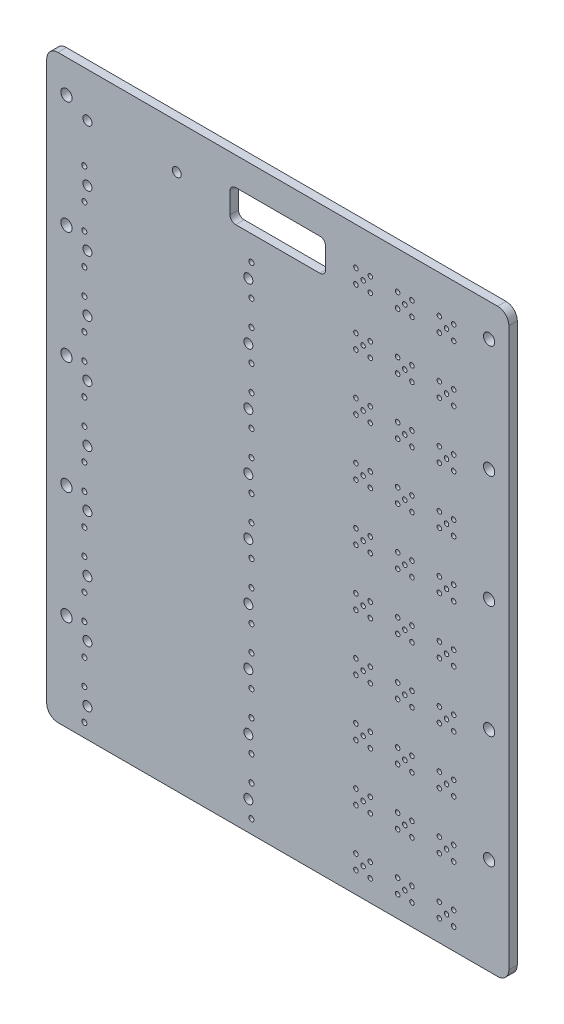
SolidWorks part; units mm, degrees
ref_plane "Front Plane" through (0, 0, 0) normal (0, 0, 1) x (1, 0, 0)
ref_plane "Top Plane" through (0, 0, 0) normal (0, 1, 0) x (1, 0, 0)
ref_plane "Right Plane" through (0, 0, 0) normal (1, 0, 0) x (0, 0, -1)
ref_plane "Plane4" through (0, 0, 0) normal (0, 0, -1) x (-1, 0, 0)
sketch "Sketch1" plane through (0, 0, 0) normal (0, 0, -1) x (-1, 0, 0)
  line L0 (7.475, 96.3) -> (-7.475, 96.3)
  line L1 (-8.475, 97.3) -> (-8.475, 101)
  line L2 (-7.475, 102) -> (7.475, 102)
  line L3 (8.475, 101) -> (8.475, 97.3)
  line L4 (39, 107) -> (-39, 107)
  line L5 (-41, 105) -> (-41, -105)
  line L6 (-39, -107) -> (39, -107)
  line L7 (41, -105) -> (41, 105)
  line L8 (8.475, -101) -> (8.475, -97.3)
  line L9 (-7.475, -102) -> (7.475, -102)
  line L10 (-8.475, -97.3) -> (-8.475, -101)
  line L11 (7.475, -96.3) -> (-7.475, -96.3)
  line L12 (41, -105) -> (41, -107) construction
  line L13 (41, -107) -> (39, -107) construction
  line L14 (41, 0) -> (-41, 0) construction
  line L15 (0, 107) -> (0, -107) construction
  arc A0 (8.475, 97.3) -> (7.475, 96.3) centre (7.475, 97.3) cw
  arc A1 (-7.475, 96.3) -> (-8.475, 97.3) centre (-7.475, 97.3) cw
  arc A2 (-8.475, 101) -> (-7.475, 102) centre (-7.475, 101) cw
  arc A3 (7.475, 102) -> (8.475, 101) centre (7.475, 101) cw
  circle A4 centre (34.325, -40.5) radius 0.45
  circle A5 centre (5.225, -43.25) radius 0.8
  circle A6 centre (-37.5, 21.2) radius 1
  circle A7 centre (5.225, -33.25) radius 0.8
  circle A8 centre (34.325, 46.5) radius 0.45
  circle A9 centre (33.775, -53.25) radius 0.8
  circle A10 centre (34.325, 82) radius 0.45
  circle A11 centre (4.675, 66.5) radius 0.45
  circle A12 centre (33.775, 19.25) radius 0.8
  circle A13 centre (4.675, -0.5) radius 0.45
  circle A14 centre (34.325, 26.5) radius 0.45
  circle A15 centre (5.225, -73.25) radius 0.8
  circle A16 centre (34.325, -66) radius 0.45
  circle A17 centre (5.225, 29.25) radius 0.8
  circle A18 centre (34.325, -80.5) radius 0.45
  circle A19 centre (34.325, 36.5) radius 0.45
  circle A20 centre (4.675, 22) radius 0.45
  circle A21 centre (33.775, -23.25) radius 0.8
  circle A22 centre (5.225, 19.25) radius 0.8
  circle A23 centre (33.775, -13.25) radius 0.8
  circle A24 centre (4.675, -10.5) radius 0.45
  circle A25 centre (34.325, 52) radius 0.45
  circle A26 centre (5.225, 89.25) radius 0.8
  circle A27 centre (5.225, -53.25) radius 0.8
  circle A28 centre (34.325, -70.5) radius 0.45
  circle A29 centre (34.325, -36) radius 0.45
  circle A30 centre (5.225, 59.25) radius 0.8
  circle A31 centre (33.775, 59.25) radius 0.8
  circle A32 centre (34.325, 32) radius 0.45
  circle A33 centre (33.775, -73.25) radius 0.8
  circle A34 centre (4.675, 46.5) radius 0.45
  circle A35 centre (4.675, 26.5) radius 0.45
  circle A36 centre (34.325, -6) radius 0.45
  circle A37 centre (34.325, -20.5) radius 0.45
  circle A38 centre (34.325, -60.5) radius 0.45
  circle A39 centre (5.225, -83.25) radius 0.8
  circle A40 centre (5.225, -13.25) radius 0.8
  circle A41 centre (33.775, -83.25) radius 0.8
  circle A42 centre (34.325, 92) radius 0.45
  circle A43 centre (33.775, -93.25) radius 0.8
  circle A44 centre (4.675, 32) radius 0.45
  circle A45 centre (4.675, 16.5) radius 0.45
  circle A46 centre (34.325, -50.5) radius 0.45
  circle A47 centre (4.675, 76.5) radius 0.45
  circle A48 centre (4.675, 82) radius 0.45
  circle A49 centre (34.325, 16.5) radius 0.45
  circle A50 centre (34.325, -56) radius 0.45
  circle A51 centre (5.225, -3.25) radius 0.8
  circle A52 centre (4.675, 36.5) radius 0.45
  circle A53 centre (4.675, -36) radius 0.45
  circle A54 centre (34.325, 86.5) radius 0.45
  circle A55 centre (33.775, 29.25) radius 0.8
  circle A56 centre (4.675, -26) radius 0.45
  circle A57 centre (4.675, -56) radius 0.45
  circle A58 centre (34.325, -30.5) radius 0.45
  circle A59 centre (33.775, 39.25) radius 0.8
  circle A60 centre (4.675, 56.5) radius 0.45
  circle A61 centre (34.325, 12) radius 0.45
  arc A62 (-39, 107) -> (-41, 105) centre (-39, 105) ccw
  arc A63 (-41, -105) -> (-39, -107) centre (-39, -105) ccw
  arc A64 (39, -107) -> (41, -105) centre (39, -105) ccw
  arc A65 (41, 105) -> (39, 107) centre (39, 105) ccw
  circle A66 centre (5.225, -63.25) radius 0.8
  circle A67 centre (4.675, -6) radius 0.45
  circle A68 centre (5.225, 49.25) radius 0.8
  circle A69 centre (4.675, -16) radius 0.45
  circle A70 centre (33.775, 9.25) radius 0.8
  circle A71 centre (4.675, -76) radius 0.45
  circle A72 centre (34.325, -76) radius 0.45
  circle A73 centre (4.675, -66) radius 0.45
  circle A74 centre (4.675, -30.5) radius 0.45
  circle A75 centre (34.325, 72) radius 0.45
  circle A76 centre (33.775, -63.25) radius 0.8
  circle A77 centre (33.775, 99.25) radius 0.8
  circle A78 centre (4.675, -86) radius 0.45
  circle A79 centre (4.675, 62) radius 0.45
  circle A80 centre (-37.5, 101.2) radius 1
  circle A81 centre (34.325, 76.5) radius 0.45
  circle A82 centre (4.675, -80.5) radius 0.45
  circle A83 centre (33.775, 49.25) radius 0.8
  circle A84 centre (4.675, 86.5) radius 0.45
  circle A85 centre (33.775, -33.25) radius 0.8
  circle A86 centre (4.675, 6.5) radius 0.45
  circle A87 centre (33.775, 79.25) radius 0.8
  circle A88 centre (34.325, -26) radius 0.45
  circle A89 centre (4.675, -60.5) radius 0.45
  circle A90 centre (4.675, 42) radius 0.45
  circle A91 centre (5.225, -23.25) radius 0.8
  circle A92 centre (34.325, 66.5) radius 0.45
  circle A93 centre (5.225, 79.25) radius 0.8
  circle A94 centre (4.675, -20.5) radius 0.45
  circle A95 centre (33.775, 89.25) radius 0.8
  circle A96 centre (17.925, -93.25) radius 0.8
  circle A97 centre (34.325, 22) radius 0.45
  circle A98 centre (4.675, 72) radius 0.45
  circle A99 centre (17.925, 99.25) radius 0.8
  circle A100 centre (4.675, 12) radius 0.45
  circle A101 centre (33.775, -3.25) radius 0.8
  circle A102 centre (34.325, 56.5) radius 0.45
  circle A103 centre (4.675, -70.5) radius 0.45
  circle A104 centre (34.325, -16) radius 0.45
  circle A105 centre (5.225, 39.25) radius 0.8
  circle A106 centre (34.325, -10.5) radius 0.45
  circle A107 centre (4.675, -50.5) radius 0.45
  circle A108 centre (-21.27, -2.0788) radius 0.4
  circle A109 centre (-31.21, -42.0789) radius 0.4
  circle A110 centre (-23.81, -44.6189) radius 0.4
  circle A111 centre (-15.14, -23.3489) radius 0.4
  circle A112 centre (-31.21, -44.6189) radius 0.4
  circle A114 centre (-16.41, -12.0788) radius 0.4
  circle A115 centre (-13.87, -24.6188) radius 0.4
  circle A116 centre (-21.27, -44.6189) radius 0.4
  circle A117 centre (-31.21, -4.6188) radius 0.4
  circle A118 centre (-15.14, -13.3489) radius 0.4
  circle A119 centre (-22.54, -13.3489) radius 0.4
  circle A120 centre (-31.21, -14.6189) radius 0.4
  circle A121 centre (-23.81, -22.0788) radius 0.4
  circle A122 centre (-29.94, -13.3489) radius 0.4
  circle A123 centre (-13.87, -12.0788) radius 0.4
  circle A124 centre (-28.67, -12.0788) radius 0.4
  circle A125 centre (-29.94, -43.3488) radius 0.4
  circle A126 centre (-22.54, -43.3488) radius 0.4
  circle A127 centre (-31.21, -2.0788) radius 0.4
  circle A128 centre (-23.81, -14.6189) radius 0.4
  circle A129 centre (-23.81, -12.0788) radius 0.4
  circle A130 centre (-16.41, -22.0788) radius 0.4
  circle A131 centre (-29.94, -3.3488) radius 0.4
  circle A132 centre (-21.27, -42.0789) radius 0.4
  circle A133 centre (-13.87, -14.6189) radius 0.4
  circle A134 centre (-15.14, -43.3488) radius 0.4
  circle A135 centre (-13.87, -42.0789) radius 0.4
  circle A136 centre (-16.41, -44.6189) radius 0.4
  circle A137 centre (-21.27, -24.6188) radius 0.4
  circle A138 centre (-23.81, -24.6188) radius 0.4
  circle A139 centre (-28.67, -4.6188) radius 0.4
  circle A140 centre (-16.41, -24.6188) radius 0.4
  circle A141 centre (-28.67, -44.6189) radius 0.4
  circle A142 centre (-21.27, -12.0788) radius 0.4
  circle A143 centre (-28.67, -42.0789) radius 0.4
  circle A144 centre (-13.87, -44.6189) radius 0.4
  circle A145 centre (-23.81, -42.0789) radius 0.4
  circle A146 centre (-28.67, -14.6189) radius 0.4
  circle A147 centre (-16.41, -42.0789) radius 0.4
  circle A148 centre (-31.21, -12.0788) radius 0.4
  circle A149 centre (-21.27, -14.6189) radius 0.4
  circle A150 centre (-13.87, -22.0788) radius 0.4
  circle A151 centre (-16.41, -14.6189) radius 0.4
  circle A152 centre (-22.54, -23.3489) radius 0.4
  circle A153 centre (-23.81, -2.0788) radius 0.4
  circle A154 centre (-23.81, -4.6188) radius 0.4
  circle A155 centre (-22.54, -3.3488) radius 0.4
  circle A156 centre (-21.27, -4.6188) radius 0.4
  circle A157 centre (-13.87, -2.0788) radius 0.4
  circle A158 centre (-16.41, -2.0788) radius 0.4
  circle A159 centre (-16.41, -4.6188) radius 0.4
  circle A160 centre (-15.14, -3.3488) radius 0.4
  circle A161 centre (-13.87, -4.6188) radius 0.4
  circle A162 centre (-28.67, -2.0788) radius 0.4
  circle A163 centre (-28.67, 10.4212) radius 0.4
  circle A164 centre (-31.21, 10.4212) radius 0.4
  circle A165 centre (-31.21, 7.8812) radius 0.4
  circle A166 centre (-29.94, 9.1512) radius 0.4
  circle A167 centre (-28.67, 7.8812) radius 0.4
  circle A168 centre (-21.27, 10.4212) radius 0.4
  circle A169 centre (-23.81, 10.4212) radius 0.4
  circle A170 centre (-23.81, 7.8812) radius 0.4
  circle A171 centre (-22.54, 9.1512) radius 0.4
  circle A172 centre (-21.27, 7.8812) radius 0.4
  circle A173 centre (-13.87, -54.6189) radius 0.4
  circle A174 centre (-15.14, -53.3489) radius 0.4
  circle A175 centre (-16.41, -54.6189) radius 0.4
  circle A176 centre (-16.41, -52.0789) radius 0.4
  circle A177 centre (-13.87, -52.0789) radius 0.4
  circle A178 centre (-21.27, -54.6189) radius 0.4
  circle A179 centre (-22.54, -53.3489) radius 0.4
  circle A180 centre (-23.81, -54.6189) radius 0.4
  circle A181 centre (-23.81, -52.0789) radius 0.4
  circle A182 centre (-21.27, -52.0789) radius 0.4
  circle A183 centre (-28.67, -54.6189) radius 0.4
  circle A184 centre (-29.94, -53.3489) radius 0.4
  circle A185 centre (-31.21, -54.6189) radius 0.4
  circle A186 centre (-31.21, -52.0789) radius 0.4
  circle A187 centre (-28.67, -52.0789) radius 0.4
  circle A188 centre (-13.87, 10.4212) radius 0.4
  circle A189 centre (-16.41, 10.4212) radius 0.4
  circle A190 centre (-16.41, 7.8812) radius 0.4
  circle A191 centre (-15.14, 9.1512) radius 0.4
  circle A192 centre (-13.87, 7.8812) radius 0.4
  circle A193 centre (-28.67, 20.4212) radius 0.4
  circle A194 centre (-31.21, 20.4212) radius 0.4
  circle A195 centre (-31.21, 17.8812) radius 0.4
  circle A196 centre (-29.94, 19.1512) radius 0.4
  circle A197 centre (-28.67, 17.8812) radius 0.4
  circle A198 centre (-21.27, 20.4212) radius 0.4
  circle A199 centre (-23.81, 20.4212) radius 0.4
  circle A200 centre (-23.81, 17.8812) radius 0.4
  circle A201 centre (-22.54, 19.1512) radius 0.4
  circle A202 centre (-21.27, 17.8812) radius 0.4
  circle A203 centre (-13.87, 20.4212) radius 0.4
  circle A204 centre (-16.41, 20.4212) radius 0.4
  circle A205 centre (-16.41, 17.8812) radius 0.4
  circle A206 centre (-15.14, 19.1512) radius 0.4
  circle A207 centre (-13.87, 17.8812) radius 0.4
  circle A208 centre (-28.67, 30.4212) radius 0.4
  circle A209 centre (-31.21, 30.4212) radius 0.4
  circle A210 centre (-31.21, 27.8812) radius 0.4
  circle A211 centre (-29.94, 29.1512) radius 0.4
  circle A212 centre (-28.67, 27.8812) radius 0.4
  circle A213 centre (-21.27, 30.4212) radius 0.4
  circle A214 centre (-23.81, 30.4212) radius 0.4
  circle A215 centre (-23.81, 27.8812) radius 0.4
  circle A216 centre (-22.54, 29.1512) radius 0.4
  circle A217 centre (-21.27, 27.8812) radius 0.4
  circle A218 centre (-13.87, 30.4212) radius 0.4
  circle A219 centre (-16.41, 30.4212) radius 0.4
  circle A220 centre (-16.41, 27.8812) radius 0.4
  circle A221 centre (-15.14, 29.1512) radius 0.4
  circle A222 centre (-13.87, 27.8812) radius 0.4
  circle A223 centre (-28.67, 40.4211) radius 0.4
  circle A224 centre (-31.21, 40.4211) radius 0.4
  circle A225 centre (-31.21, 37.8812) radius 0.4
  circle A226 centre (-29.94, 39.1512) radius 0.4
  circle A227 centre (-28.67, 37.8812) radius 0.4
  circle A228 centre (-13.87, -64.6188) radius 0.4
  circle A229 centre (-15.14, -63.3488) radius 0.4
  circle A230 centre (-16.41, -64.6188) radius 0.4
  circle A231 centre (-16.41, -62.0789) radius 0.4
  circle A232 centre (-13.87, -62.0789) radius 0.4
  circle A233 centre (-21.27, -64.6188) radius 0.4
  circle A234 centre (-22.54, -63.3488) radius 0.4
  circle A235 centre (-23.81, -64.6188) radius 0.4
  circle A236 centre (-23.81, -62.0789) radius 0.4
  circle A237 centre (-21.27, -62.0789) radius 0.4
  circle A238 centre (-28.67, -64.6188) radius 0.4
  circle A239 centre (-29.94, -63.3488) radius 0.4
  circle A240 centre (-31.21, -64.6188) radius 0.4
  circle A241 centre (-31.21, -62.0789) radius 0.4
  circle A242 centre (-28.67, -62.0789) radius 0.4
  circle A243 centre (-21.27, 40.4211) radius 0.4
  circle A244 centre (-23.81, 40.4211) radius 0.4
  circle A245 centre (-23.81, 37.8812) radius 0.4
  circle A246 centre (-22.54, 39.1512) radius 0.4
  circle A247 centre (-21.27, 37.8812) radius 0.4
  circle A248 centre (-13.87, 40.4211) radius 0.4
  circle A249 centre (-16.41, 40.4211) radius 0.4
  circle A250 centre (-16.41, 37.8812) radius 0.4
  circle A251 centre (-15.14, 39.1512) radius 0.4
  circle A252 centre (-13.87, 37.8812) radius 0.4
  circle A253 centre (-28.67, 50.4211) radius 0.4
  circle A254 centre (-31.21, 50.4211) radius 0.4
  circle A255 centre (-31.21, 47.8811) radius 0.4
  circle A256 centre (-29.94, 49.1512) radius 0.4
  circle A257 centre (-28.67, 47.8811) radius 0.4
  circle A258 centre (-21.27, 50.4211) radius 0.4
  circle A259 centre (-23.81, 50.4211) radius 0.4
  circle A260 centre (-23.81, 47.8811) radius 0.4
  circle A261 centre (-22.54, 49.1512) radius 0.4
  circle A262 centre (-21.27, 47.8811) radius 0.4
  circle A263 centre (-13.87, 50.4211) radius 0.4
  circle A264 centre (-16.41, 50.4211) radius 0.4
  circle A265 centre (-16.41, 47.8811) radius 0.4
  circle A266 centre (-15.14, 49.1512) radius 0.4
  circle A267 centre (-13.87, 47.8811) radius 0.4
  circle A268 centre (-28.67, 60.4211) radius 0.4
  circle A269 centre (-31.21, 60.4211) radius 0.4
  circle A270 centre (-31.21, 57.8811) radius 0.4
  circle A271 centre (-29.94, 59.1512) radius 0.4
  circle A272 centre (-28.67, 57.8811) radius 0.4
  circle A273 centre (-21.27, 60.4211) radius 0.4
  circle A274 centre (-23.81, 60.4211) radius 0.4
  circle A275 centre (-23.81, 57.8811) radius 0.4
  circle A276 centre (-22.54, 59.1512) radius 0.4
  circle A277 centre (-21.27, 57.8811) radius 0.4
  circle A278 centre (-13.87, 60.4211) radius 0.4
  circle A279 centre (-16.41, 60.4211) radius 0.4
  circle A280 centre (-16.41, 57.8811) radius 0.4
  circle A281 centre (-15.14, 59.1512) radius 0.4
  circle A282 centre (-13.87, 57.8811) radius 0.4
  circle A283 centre (-13.87, -74.6188) radius 0.4
  circle A284 centre (-15.14, -73.3489) radius 0.4
  circle A285 centre (-16.41, -74.6188) radius 0.4
  circle A286 centre (-16.41, -72.0789) radius 0.4
  circle A287 centre (-13.87, -72.0789) radius 0.4
  circle A288 centre (-21.27, -74.6188) radius 0.4
  circle A289 centre (-22.54, -73.3489) radius 0.4
  circle A290 centre (-23.81, -74.6188) radius 0.4
  circle A291 centre (-23.81, -72.0789) radius 0.4
  circle A292 centre (-21.27, -72.0789) radius 0.4
  circle A293 centre (-28.67, -74.6188) radius 0.4
  circle A294 centre (-29.94, -73.3489) radius 0.4
  circle A295 centre (-31.21, -74.6188) radius 0.4
  circle A296 centre (-31.21, -72.0789) radius 0.4
  circle A297 centre (-28.67, -72.0789) radius 0.4
  circle A298 centre (-28.67, 70.4211) radius 0.4
  circle A299 centre (-31.21, 70.4211) radius 0.4
  circle A300 centre (-31.21, 67.8812) radius 0.4
  circle A301 centre (-29.94, 69.1512) radius 0.4
  circle A302 centre (-28.67, 67.8812) radius 0.4
  circle A303 centre (-21.27, 70.4211) radius 0.4
  circle A304 centre (-23.81, 70.4211) radius 0.4
  circle A305 centre (-23.81, 67.8812) radius 0.4
  circle A306 centre (-22.54, 69.1512) radius 0.4
  circle A307 centre (-21.27, 67.8812) radius 0.4
  circle A308 centre (-13.87, 70.4211) radius 0.4
  circle A309 centre (-16.41, 70.4211) radius 0.4
  circle A310 centre (-16.41, 67.8812) radius 0.4
  circle A311 centre (-15.14, 69.1512) radius 0.4
  circle A312 centre (-13.87, 67.8812) radius 0.4
  circle A313 centre (-28.67, 80.4211) radius 0.4
  circle A314 centre (-31.21, 80.4211) radius 0.4
  circle A315 centre (-31.21, 77.8812) radius 0.4
  circle A316 centre (-29.94, 79.1512) radius 0.4
  circle A317 centre (-28.67, 77.8812) radius 0.4
  circle A318 centre (-21.27, 80.4211) radius 0.4
  circle A319 centre (-23.81, 80.4211) radius 0.4
  circle A320 centre (-23.81, 77.8812) radius 0.4
  circle A321 centre (-22.54, 79.1512) radius 0.4
  circle A322 centre (-21.27, 77.8812) radius 0.4
  circle A323 centre (-13.87, 80.4211) radius 0.4
  circle A324 centre (-16.41, 80.4211) radius 0.4
  circle A325 centre (-16.41, 77.8812) radius 0.4
  circle A326 centre (-15.14, 79.1512) radius 0.4
  circle A327 centre (-13.87, 77.8812) radius 0.4
  circle A328 centre (-28.67, 90.4212) radius 0.4
  circle A329 centre (-31.21, 90.4212) radius 0.4
  circle A330 centre (-31.21, 87.8812) radius 0.4
  circle A331 centre (-29.94, 89.1512) radius 0.4
  circle A332 centre (-28.67, 87.8812) radius 0.4
  circle A333 centre (-21.27, 90.4212) radius 0.4
  circle A334 centre (-23.81, 90.4212) radius 0.4
  circle A335 centre (-23.81, 87.8812) radius 0.4
  circle A336 centre (-22.54, 89.1512) radius 0.4
  circle A337 centre (-21.27, 87.8812) radius 0.4
  circle A338 centre (-13.87, -84.6188) radius 0.4
  circle A339 centre (-15.14, -83.3488) radius 0.4
  circle A340 centre (-16.41, -84.6188) radius 0.4
  circle A341 centre (-16.41, -82.0789) radius 0.4
  circle A342 centre (-13.87, -82.0789) radius 0.4
  circle A343 centre (-21.27, -84.6188) radius 0.4
  circle A344 centre (-22.54, -83.3488) radius 0.4
  circle A345 centre (-23.81, -84.6188) radius 0.4
  circle A346 centre (-23.81, -82.0789) radius 0.4
  circle A347 centre (-21.27, -82.0789) radius 0.4
  circle A348 centre (-28.67, -84.6188) radius 0.4
  circle A349 centre (-29.94, -83.3488) radius 0.4
  circle A350 centre (-31.21, -84.6188) radius 0.4
  circle A351 centre (-31.21, -82.0789) radius 0.4
  circle A352 centre (-28.67, -82.0789) radius 0.4
  circle A353 centre (-13.87, 90.4212) radius 0.4
  circle A354 centre (-16.41, 90.4212) radius 0.4
  circle A355 centre (-16.41, 87.8812) radius 0.4
  circle A356 centre (-15.14, 89.1512) radius 0.4
  circle A357 centre (-13.87, 87.8812) radius 0.4
  circle A358 centre (4.675, -40.5) radius 0.45
  circle A359 centre (34.325, -46) radius 0.45
  circle A360 centre (34.325, 6.5) radius 0.45
  circle A361 centre (4.675, 92) radius 0.45
  circle A362 centre (34.325, 62) radius 0.45
  circle A363 centre (34.325, -86) radius 0.45
  circle A364 centre (4.675, -46) radius 0.45
  circle A365 centre (34.325, 42) radius 0.45
  circle A366 centre (5.225, 69.25) radius 0.8
  circle A367 centre (33.775, 69.25) radius 0.8
  circle A368 centre (33.775, -43.25) radius 0.8
  circle A369 centre (5.225, 9.25) radius 0.8
  circle A370 centre (4.675, 52) radius 0.45
  circle A371 centre (34.325, -0.5) radius 0.45
  circle A372 centre (-13.87, -92.0789) radius 0.4
  circle A373 centre (-31.21, -94.6188) radius 0.4
  circle A374 centre (-28.67, -92.0789) radius 0.4
  circle A375 centre (-28.67, -94.6188) radius 0.4
  circle A376 centre (-29.94, -93.3488) radius 0.4
  circle A377 centre (-23.81, -92.0789) radius 0.4
  circle A378 centre (-16.41, -94.6188) radius 0.4
  circle A379 centre (-21.27, -94.6188) radius 0.4
  circle A380 centre (-21.27, -92.0789) radius 0.4
  circle A381 centre (-23.81, -94.6188) radius 0.4
  circle A382 centre (-16.41, -92.0789) radius 0.4
  circle A383 centre (-31.21, -92.0789) radius 0.4
  circle A384 centre (-22.54, -93.3488) radius 0.4
  circle A385 centre (-13.87, -94.6188) radius 0.4
  circle A386 centre (-15.14, -93.3488) radius 0.4
  circle A387 centre (-21.27, -22.0788) radius 0.4
  circle A388 centre (-28.67, -24.6188) radius 0.4
  circle A389 centre (-29.94, -23.3489) radius 0.4
  circle A390 centre (-31.21, -24.6188) radius 0.4
  circle A391 centre (-31.21, -22.0788) radius 0.4
  circle A392 centre (-28.67, -22.0788) radius 0.4
  circle A393 centre (-13.87, -34.6189) radius 0.4
  circle A394 centre (-15.14, -33.3488) radius 0.4
  circle A395 centre (-16.41, -34.6189) radius 0.4
  circle A396 centre (-16.41, -32.0789) radius 0.4
  circle A397 centre (-13.87, -32.0789) radius 0.4
  circle A398 centre (-21.27, -34.6189) radius 0.4
  circle A399 centre (-22.54, -33.3488) radius 0.4
  circle A400 centre (-23.81, -34.6189) radius 0.4
  circle A401 centre (-23.81, -32.0789) radius 0.4
  circle A402 centre (-21.27, -32.0789) radius 0.4
  circle A403 centre (-28.67, -34.6189) radius 0.4
  circle A404 centre (-29.94, -33.3488) radius 0.4
  circle A405 centre (-31.21, -34.6189) radius 0.4
  circle A406 centre (-31.21, -32.0789) radius 0.4
  circle A407 centre (-28.67, -32.0789) radius 0.4
  circle A408 centre (-37.5, -81.2) radius 1
  circle A409 centre (37.5, 81.2) radius 1
  circle A412 centre (-37.5, 41.2) radius 1
  circle A413 centre (-37.5, -41.2) radius 1
  circle A414 centre (-37.5, -101.2) radius 1
  circle A415 centre (-37.5, 61.2) radius 1
  circle A416 centre (37.5, 61.2) radius 1
  circle A417 centre (-37.5, 81.2) radius 1
  circle A420 centre (-37.5, -61.2) radius 1
  circle A421 centre (37.5, 41.2) radius 1
  circle A422 centre (-37.5, -21.2) radius 1
  circle A423 centre (37.5, 101.2) radius 1
  circle A424 centre (37.5, 21.2) radius 1
  arc A425 (8.475, -97.3) -> (7.475, -96.3) centre (7.475, -97.3) ccw
  arc A426 (7.475, -102) -> (8.475, -101) centre (7.475, -101) ccw
  arc A427 (-8.475, -101) -> (-7.475, -102) centre (-7.475, -101) ccw
  arc A428 (-7.475, -96.3) -> (-8.475, -97.3) centre (-7.475, -97.3) ccw
  point P876 (0, 102)
  dimension "D3" = 2
  dimension "D4" = 1
  dimension "D9" = 2
  dimension "D1" = 82
  dimension "D2" = 214
  dimension "D5" = 16.95
  dimension "D6" = 5.7
  dimension "D7" = 5
  dimension "D8" = 5
  dimension "D10" = 5.8
  dimension "D11" = 3.5
  dimension "D12" = 20
extrude "Boss-Extrude1" [suppressed] add sketch "Sketch1" against normal blind 1.5
sketch "Sketch2" plane through (0, 0, 0) normal (0, 0, 1) x (1, 0, 0)
  line L0 (82, 103) -> (0, 103)
  line L1 (0, 103) -> (0, 0)
  line L2 (0, 0) -> (82, 0)
  line L3 (82, 0) -> (82, 103)
  dimension "D1" = 82
  dimension "D2" = 103
extrude "mainBoard" add sketch "Sketch2" along normal blind 1.5
ref_plane "X_mirror" through (41, 0, 0) normal (-1, 0, 0) x (0, 0, 1)
sketch "Sketch3" plane through (0, 0, 1.5) normal (0, 0, 1) x (1, 0, 0)
  line L0 (82, 103) -> (0, 103) construction
  line L1 (41, 103) -> (41, 0) construction
  line L2 (0, 0) -> (82, 0) construction
  line L5 (32.525, 98) -> (49.475, 98)
  line L6 (32.525, 98) -> (32.525, 92.3)
  line L7 (32.525, 92.3) -> (49.475, 92.3)
  line L8 (49.475, 98) -> (49.475, 92.3)
  point P6 (41, 98)
  dimension "D1" = 5
  dimension "D3" = 16.95
  dimension "D4" = 5.7
extrude "solarHole" cut sketch "Sketch3" against normal through all
fillet "Fillet1" radius 2 4 edges at (0, 0, 0.75) (82, 0, 0.75) (82, 103, 0.75) (0, 103, 0.75)
fillet "Fillet2" radius 1 4 edges at (49.475, 92.3, 0.75) (49.475, 98, 0.75) (32.525, 92.3, 0.75) (32.525, 98, 0.75)
hole_wizard "Ø2.0mm Hole_screw" positions "Sketch4" profile "Sketch5" hole size "Ø2.0" standard "ANSI Metric"
sketch "Sketch4" plane through (0, 0, 1.5) normal (0, 0, 1) x (1, 0, 0)
  line L0 (80, 103) -> (2, 103) construction
  line L1 (0, 101) -> (0, 2) construction
  point P0 (3.5, 97.2)
  dimension "D1" = 5.8
  dimension "D2" = 3.5
sketch "Sketch5" plane through (3.5, 97.2, 1.5) normal (1, 0, 0) x (0, -1, 0)
  line L0 (0, 0) -> (0, 10.1259)
  line L1 (0, 10.1259) -> (1, 9.525)
  line L2 (1, 9.525) -> (1, 0)
  line L5 (1, 0) -> (0, 0)
  line L10 (0, 10.1259) -> (-1, 9.525) construction
  line L11 (0, -6.35) -> (0, 107.95) construction
  dimension "Hole Dia." = 2
  dimension "Hole Depth" = 9.525
  dimension "Drill Angle" = 118
hole_wizard "Ø1.6mm Hole_20pin" positions "Sketch12" profile "Sketch13" hole size "Ø1.5" standard "ANSI Metric"
sketch "Sketch12" plane through (0, 0, 1.5) normal (0, 0, 1) x (1, 0, 0)
  line L0 (80, 103) -> (2, 103) construction
  line L1 (0, 101) -> (0, 2) construction
  point P0 (7.225, 95.15)
  point P2 (23.075, 95.15)
  dimension "D1" = 15.85
  dimension "D2" = 7.85
  dimension "D3" = 7.225
sketch "Sketch13" plane through (7.225, 95.15, 1.5) normal (1, 0, 0) x (0, -1, 0)
  line L0 (0, 0) -> (0, 10.0057)
  line L1 (0, 10.0057) -> (0.8, 9.525)
  line L2 (0.8, 9.525) -> (0.8, 0)
  line L5 (0.8, 0) -> (0, 0)
  line L10 (0, 10.0057) -> (-0.8, 9.525) construction
  line L11 (0, -6.35) -> (0, 107.95) construction
  dimension "Hole Dia." = 1.6
  dimension "Hole Depth" = 9.525
  dimension "Drill Angle" = 118
hole_wizard "Ø1.6mm Hole_40pn_big" positions "Sketch6" profile "Sketch7" hole size "Ø1.5" standard "ANSI Metric"
sketch "Sketch6" plane through (0, 0, 1.5) normal (0, 0, 1) x (1, 0, 0)
  line L0 (0, 101) -> (0, 2) construction
  line L1 (80, 103) -> (2, 103) construction
  point P14 (7.225, 85.15)
  point P16 (35.775, 85.15)
  dimension "D1" = 7.225
  dimension "D7" = 17.85
  dimension "D8" = 28.55
sketch "Sketch7" plane through (7.225, 85.15, 1.5) normal (1, 0, 0) x (0, -1, 0)
  line L0 (0, 0) -> (0, 10.0057)
  line L1 (0, 10.0057) -> (0.8, 9.525)
  line L2 (0.8, 9.525) -> (0.8, 0)
  line L5 (0.8, 0) -> (0, 0)
  line L10 (0, 10.0057) -> (-0.8, 9.525) construction
  line L11 (0, -6.35) -> (0, 107.95) construction
  dimension "Hole Dia." = 1.6
  dimension "Hole Depth" = 9.525
  dimension "Drill Angle" = 118
hole_wizard "Ø0.9mm Hole_40pin_tiny" positions "Sketch10" profile "Sketch11" hole size "Ø1.5" standard "ANSI Metric"
sketch "Sketch10" plane through (0, 0, 1.5) normal (0, 0, 1) x (1, 0, 0)
  line L1 (7.225, 85.15) -> (35.775, 85.15) construction
  line L3 (21.5, -11.0236) -> (21.5, 181.3236) construction
  circle A0 centre (7.225, 85.15) radius 0.8 construction
  point P0 (6.675, 87.9)
  point P24 (21.5, 85.15)
  point P25 (21.5, 85.15)
  point P27 (6.675, 82.4)
  point P29 (36.325, 87.9)
  point P30 (36.325, 82.4)
  dimension "D1" = 0.55
  dimension "D2" = 5.5
sketch "Sketch11" plane through (6.675, 87.9, 1.5) normal (1, 0, 0) x (0, -1, 0)
  line L0 (0, 0) -> (0, 9.7954)
  line L1 (0, 9.7954) -> (0.45, 9.525)
  line L2 (0.45, 9.525) -> (0.45, 0)
  line L5 (0.45, 0) -> (0, 0)
  line L10 (0, 9.7954) -> (-0.45, 9.525) construction
  line L11 (0, -6.35) -> (0, 107.95) construction
  dimension "Hole Dia." = 0.9
  dimension "Hole Depth" = 9.525
  dimension "Drill Angle" = 118
hole_wizard "Ø0.8mm MMCX Hole" positions "Sketch8" profile "Sketch9" hole size "Ø1.0" standard "ANSI Metric"
sketch "Sketch8" plane through (0, 0, 1.5) normal (0, 0, 1) x (1, 0, 0)
  line L0 (69.67, 86.32) -> (72.21, 83.78) construction
  line L2 (80, 103) -> (2, 103) construction
  line L3 (82, 2) -> (82, 101) construction
  point P0 (70.94, 85.05)
  point P2 (69.67, 86.32)
  point P4 (72.21, 86.32)
  point P6 (72.21, 83.78)
  point P8 (69.67, 83.78)
  point P21 (70.94, 85.05)
  dimension "D1" = 2.54
  dimension "D2" = 2.54
  dimension "D3" = 17.95
  dimension "D4" = 11.06
sketch "Sketch9" plane through (70.94, 85.05, 1.5) normal (1, 0, 0) x (0, -1, 0)
  line L0 (0, 0) -> (0, 9.7653)
  line L1 (0, 9.7653) -> (0.4, 9.525)
  line L2 (0.4, 9.525) -> (0.4, 0)
  line L5 (0.4, 0) -> (0, 0)
  line L10 (0, 9.7653) -> (-0.4, 9.525) construction
  line L11 (0, -6.35) -> (0, 107.95) construction
  dimension "Hole Dia." = 0.8
  dimension "Hole Depth" = 9.525
  dimension "Drill Angle" = 118
pattern_linear "MMCX_intra-card" count 3 spacing 7.4 along (-1, 0, 0) of "Ø0.8mm MMCX Hole"
pattern_linear "Zpos_block" count 9 spacing 10 along (0, -1, 0) of "MMCX_intra-card", "Ø0.9mm Hole_40pin_tiny", "Ø1.6mm Hole_40pn_big"
pattern_linear "Zpos_antennaMMCX" count 2 spacing 10 along (0, 1, 0) of "MMCX_intra-card"
pattern_linear "screwHoles_intra-rail" count 5 spacing 20 along (0, -1, 0) of "Ø2.0mm Hole_screw"
pattern_linear "Zneg_block" [suppressed] count 2 spacing 92.4 of bodies 107
pattern_linear "Zneg_antennaMMCX" [suppressed] count 3 spacing 10 of bodies 107
ref_plane "Y_mirror" through (0, 51.5, 0) normal (0, 1, 0) x (1, 0, 0)
mirror "screwHoles_trans-rail" about plane through (41, 0, 0) normal (-1, 0, 0) of "Ø2.0mm Hole_screw", "screwHoles_intra-rail"
mirror "screwHoles_Zneg_block" [suppressed] about plane through (0, 51.5, 0) normal (0, 1, 0)
